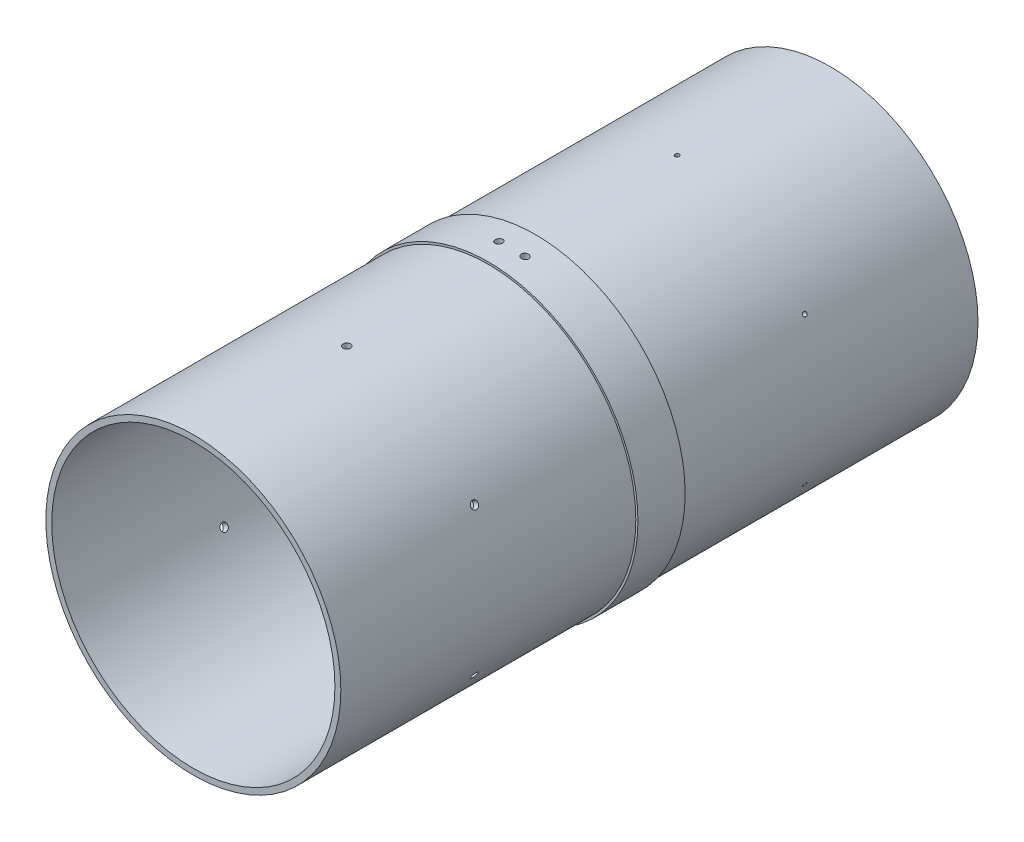
SolidWorks part; units mm, degrees
ref_plane "Front Plane" through (0, 0, 0) normal (0, 0, 1) x (1, 0, 0)
ref_plane "Top Plane" through (0, 0, 0) normal (0, 1, 0) x (1, 0, 0)
ref_plane "Right Plane" through (0, 0, 0) normal (1, 0, 0) x (0, 0, -1)
sketch "Sketch1" plane through (0, 0, 0) normal (0, 0, 1) x (1, 0, 0)
  circle A0 centre (0, 0) radius 79.375
  circle A1 centre (0, 0) radius 76.2
  dimension "D1" = 158.75
  dimension "D2" = 3.175
extrude "Boss-Extrude1" add sketch "Sketch1" along normal blind 342.9
ref_plane "Plane1" through (0, 0, 171.45) normal (0, 0, 1) x (1, 0, 0)
sketch "Sketch2" plane through (0, 0, 171.45) normal (0, 0, 1) x (1, 0, 0)
  circle A0 centre (0, 0) radius 79.375 construction
  circle A1 centre (0, 0) radius 79.375
  circle A2 centre (0, 0) radius 80.518
extrude "Boss-Extrude2" add sketch "Sketch2" against normal mid plane 25.4
sketch "Sketch5" plane through (0, 0, 171.45) normal (0, 0, 1) x (1, 0, 0)
  line L0 (0, 0) -> (0, 47.1719) construction
  line L1 (0, 0) -> (7.0176, 80.2116) construction
  circle A1 centre (0, 0) radius 80.518 construction
  dimension "D1" = 5
ref_plane "Plane2" through (7.0176, 80.2116, 0) normal (0.0872, 0.9962, 0) x (0, 0, 1)
hole_wizard "5/32 (0.15625) Diameter Hole1" positions "Sketch9" profile "Sketch10" hole size "5/32" standard "ANSI Inch" end condition up to next
sketch "Sketch9" plane through (7.0176, 80.2116, 0) normal (0.0872, 0.9962, 0) x (0, 0, 1)
  point P0 (171.45, 0)
sketch "Sketch10" plane through (7.0176, 80.2116, 171.45) normal (0, 0, 1) x (-0.9962, 0.0872, 0)
  line L0 (0, 0) -> (0, 4.318)
  line L1 (0, 4.318) -> (1.9844, 4.318)
  line L2 (1.9844, 4.318) -> (1.9844, 0)
  line L5 (1.9844, 0) -> (0, 0)
  line L11 (0, -6.35) -> (0, 107.95) construction
  dimension "Thru Hole Dia." = 3.9688
  dimension "Thru Hole Depth" = 4.318
mirror "Mirror1" about plane through (0, 0, 0) normal (1, 0, 0) of "5/32 (0.15625) Diameter Hole1"
ref_plane "Plane3" through (0, 79.375, 0) normal (0, 1, 0) x (1, 0, 0)
sketch "Sketch11" plane through (0, 79.375, 0) normal (0, 1, 0) x (1, 0, 0)
  line L0 (80.518, -158.75) -> (-80.518, -158.75) construction
  point P0 (0, -82.55)
  dimension "D1" = 76.2
hole_wizard "#4-40 Tapped Hole1" positions "Sketch12" profile "Sketch13" tap size "#4-40" standard "ANSI Inch" end condition up to next
sketch "Sketch12" plane through (0, 79.375, 0) normal (0, 1, 0) x (1, 0, 0)
  point P0 (0, -82.55)
sketch "Sketch13" plane through (0, 79.375, 82.55) normal (1, 0, 0) x (0, 0, 1)
  line L0 (0, 0) -> (0, 3.175)
  line L1 (0, 3.175) -> (1.1303, 3.175)
  line L2 (1.1303, 3.175) -> (1.1303, 0)
  line L5 (1.1303, 0) -> (0, 0)
  line L11 (0, -6.35) -> (0, 107.95) construction
  dimension "Thru Tap Drill Dia." = 2.2606
  dimension "Thru Tap Drill Depth" = 3.175
cosmetic thread "Hole Thread1" parameters "D2"=2.8448
pattern_circular "CirPattern1" count 6 over 360 about axis through (0, 0, 0) along (0, 0, 1) of "#4-40 Tapped Hole1"
cosmetic thread "Hole Thread2" parameters "D2"=2.8448
cosmetic thread "Hole Thread3" parameters "D2"=2.8448
cosmetic thread "Hole Thread4" parameters "D2"=2.8448
cosmetic thread "Hole Thread9" parameters "D2"=2.8448
cosmetic thread "Hole Thread10" parameters "D2"=2.8448
sketch "Sketch14" plane through (0, 79.375, 0) normal (0, 1, 0) x (1, 0, 0)
  line L0 (-79.375, -184.15) -> (79.375, -184.15) construction
  point P0 (0, -260.35)
  dimension "D1" = 76.2
hole_wizard "#10-32 Tapped Hole1" positions "Sketch15" profile "Sketch16" tap size "#10-32" standard "ANSI Inch" end condition up to next
sketch "Sketch15" plane through (0, 79.375, 0) normal (0, 1, 0) x (1, 0, 0)
  point P0 (0, -260.35)
sketch "Sketch16" plane through (0, 79.375, 260.35) normal (1, 0, 0) x (0, 0, 1)
  line L0 (0, 0) -> (0, 3.175)
  line L1 (0, 3.175) -> (2.0193, 3.175)
  line L2 (2.0193, 3.175) -> (2.0193, 0)
  line L5 (2.0193, 0) -> (0, 0)
  line L11 (0, -6.35) -> (0, 107.95) construction
  dimension "Thru Tap Drill Dia." = 4.0386
  dimension "Thru Tap Drill Depth" = 3.175
cosmetic thread "Hole Thread5" parameters "D2"=4.826
pattern_circular "CirPattern2" count 6 over 360 about axis through (0, 0, 342.9) along (0, 0, 1) of "#10-32 Tapped Hole1"
cosmetic thread "Hole Thread6" parameters "D2"=4.826
cosmetic thread "Hole Thread7" parameters "D2"=4.826
cosmetic thread "Hole Thread8" parameters "D2"=4.826
cosmetic thread "Hole Thread11" parameters "D2"=4.826
cosmetic thread "Hole Thread12" parameters "D2"=4.826
